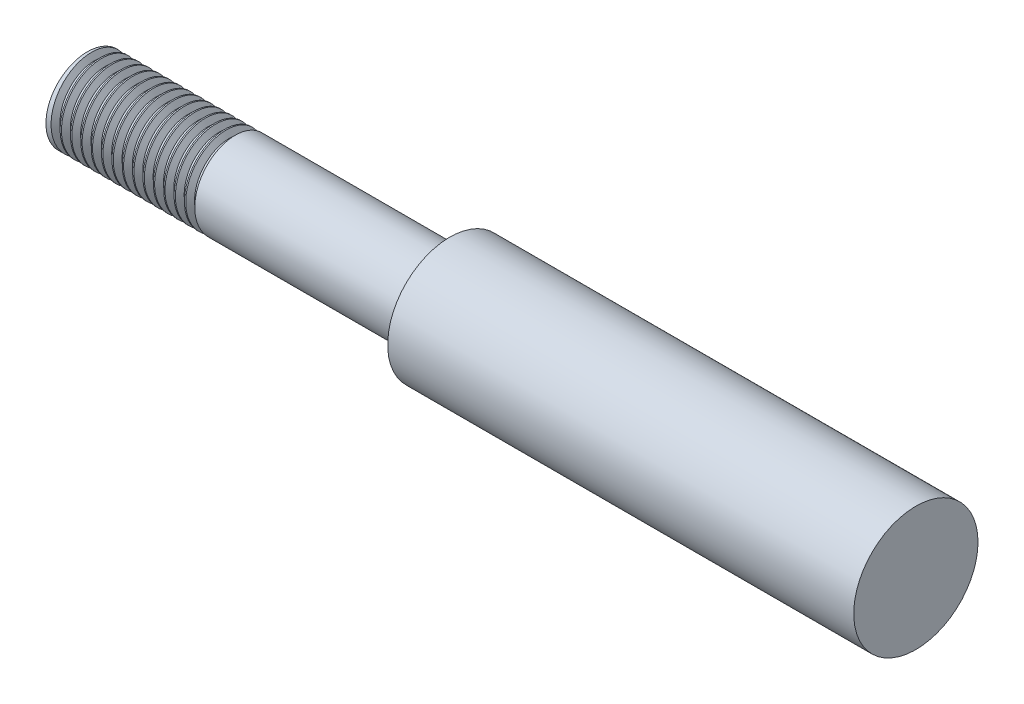
SolidWorks part; units mm, degrees
material "201 Annealed Stainless Steel (SS)"
ref_plane "Front Plane" through (0, 0, 0) normal (0, 0, 1) x (1, 0, 0)
ref_plane "Top Plane" through (0, 0, 0) normal (0, 1, 0) x (1, 0, 0)
ref_plane "Right Plane" through (0, 0, 0) normal (1, 0, 0) x (0, 0, -1)
sketch "Sketch1" plane through (0, 0, 0) normal (1, 0, 0) x (0, 0, -1)
  circle A0 centre (0, 0) radius 6
  dimension "D1" = 12
extrude "Boss-Extrude1" add sketch "Sketch1" against normal blind 45
sketch "Sketch2" plane through (-45, 0, 0) normal (-1, 0, 0) x (0, 0, 1)
  circle A0 centre (0, 0) radius 4
  dimension "D1" = 8
extrude "Boss-Extrude2" add sketch "Sketch2" along normal blind 35
thread "Thread1" pitch 1 method cut profile "Thread Profile1" start angle 0, offset 0, length 14, pitch 1, diameter 8
ref_plane "Plane1" through (-80, 0, -4) normal (0, -1, 0) x (0, 0, -1)
sketch "Thread Profile1" plane through (-80, 0, -4) normal (0, -1, 0) x (0, 0, -1)
  line L0 (0, 0) -> (0, 1) construction
  line L11 (0, 0) -> (0, 0.875)
  line L12 (0, 0.875) -> (-0.5413, 0.5625)
  line L13 (-0.5413, 0.5625) -> (-0.5413, 0.3125)
  line L15 (-0.5413, 0.3125) -> (0, 0)
  line L17 (-0.5413, 0.4375) -> (0, 0.4375) construction
  point P2 (0, 0)
  dimension "Pitch" = 1
  dimension "Profile_Angle" = 60
  dimension "Profile_Land" = 0.25
  dimension "Profile_Height" = 0.5413
